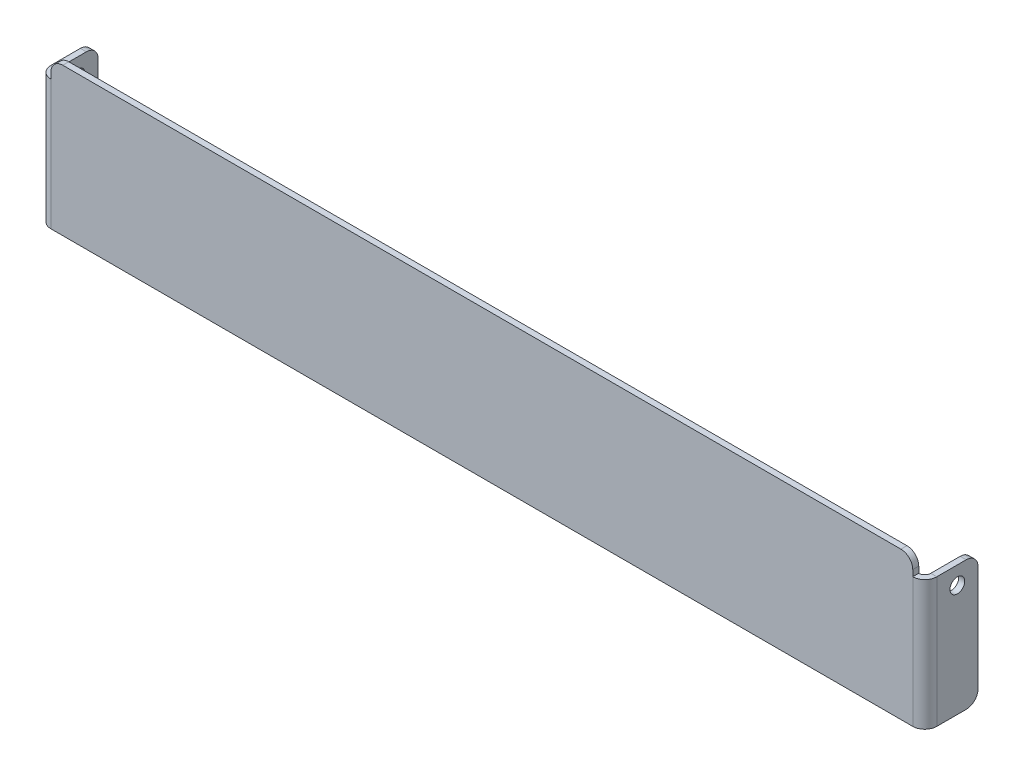
SolidWorks part; units mm, degrees
note: The reader was unsure of these and kept them because the rebuilt part matched: flange length of "Edge-Flange1".
ref_plane "Front Plane" through (0, 0, 0) normal (0, 0, 1) x (1, 0, 0)
ref_plane "Top Plane" through (0, 0, 0) normal (0, 1, 0) x (1, 0, 0)
ref_plane "Right Plane" through (0, 0, 0) normal (1, 0, 0) x (0, 0, -1)
sketch "Sketch2" plane through (0, 0, 0) normal (0, 0, 1) x (1, 0, 0)
  line L0 (75, -24.996) -> (-75, -24.996) construction
  line L1 (-72.968, -24.996) -> (0, -24.996)
  line L2 (-72.968, -24.996) -> (-72.968, 0)
  line L3 (-72.968, 0) -> (0, 0)
  line L4 (0, -24.996) -> (0, 0)
  dimension "D1" = 72.968
base flange "Base-Flange1" sketch "Sketch2" thickness 1.016 reverse thickness direction no parameters "D1"=1.016
edge flange "Edge-Flange1" sketch "Sketch27" flange angle 90 flange length 8 flange position bend outside bend radius 1.016 thickness 1.016 relief rectangular parameters "D6"=10, "D8"=1
bend "EdgeBend3" bend radius 1.016 bend angle 90 parameters "D5"=1
sketch "Sketch27" plane through (-72.968, 0, -1.016) normal (-1, 0, 0) x (0, 1, 0)
  line L2 (-3.048, 0) -> (-3.048, 8)
  line L3 (-3.048, 8) -> (-24.996, 8)
  line L4 (-24.996, 8) -> (-24.996, 0)
  line L5 (0, 0) -> (-24.996, 0) construction
  line L6 (-3.048, 0) -> (-24.996, 0)
  line L7 (0, 0) -> (0, -1.016) construction
  point P7 (0, -0.508)
  dimension "D1" = 3.048
fillet "Fillet1" radius 2 3 edges at (-74.492, -24.996, -9.016) (-74.492, -3.048, -9.016) (-72.968, 0, -0.508)
sketch "Sketch15" plane through (-75, 0, 0) normal (1, 0, 0) x (0, 0, -1)
  line L0 (9.016, -6.048) -> (5.524, -6.048) construction
  line L2 (5.524, -6.048) -> (2.032, -6.048) construction
  line L7 (2.032, -3.048) -> (7.016, -3.048) construction
  dimension "D1" = 3
hole_wizard "Tap Drill for M3x0.5 Tap1" positions "Sketch31" profile "Sketch32" hole size "M3x0.5" standard "ANSI Metric" end condition through all
sketch "Sketch31" plane through (-75, 0, 0) normal (-1, 0, 0) x (0, 0, 1)
  point P0 (-5.524, -6.048)
sketch "Sketch32" plane through (-75, -6.048, -5.524) normal (0, 1, 0) x (0, 0, 1)
  line L0 (0, 0) -> (0, 75)
  line L1 (0, 75) -> (1.25, 75)
  line L2 (1.25, 75) -> (1.25, 0)
  line L5 (1.25, 0) -> (0, 0)
  line L11 (0, -6.35) -> (0, 107.95) construction
  dimension "Thru Hole Dia." = 2.5
  dimension "Thru Hole Depth" = 75
mirror "Mirror1" about plane through (0, -24.996, -1.016) normal (1, 0, 0) of bodies 105
bend "MirrorBend1" bend radius 1.016 bend angle 90 parameters "D5"=2
sketch "Bend-Lines1" [suppressed] plane through (0, 0, 0) normal (0, 1, 0) x (1, 0, 0)
sketch "Bounding-Box1" [suppressed] plane through (0, 0, 0) normal (0, 1, 0) x (1, 0, 0)
sheet metal parameters "Sheet-Metal1" thickness 1.016 parameters "D1"=1.016
flat pattern "Flat-Pattern1" [suppressed]
sketch "Bend-Lines2" plane through (0, 0, 0) normal (0, 1, 0) x (1, 0, 0)
sketch3d "Bounding-Box2" [suppressed]
  line L0 (-75, -15.996, 0) -> (0, -15.996, 0) construction
  line L1 (-75, 0, 0) -> (0, 0, 0) construction
  line L2 (-75, -15.996, 0) -> (-75, 0, 0) construction
  line L3 (0, -15.996, 0) -> (0, 0, 0) construction
sheet metal parameters "Sheet-Metal2" thickness 1.016 parameters "D1"=1.016
flat pattern "Flat-Pattern1"
sketch "Bend-Lines2" plane through (0, 0, 0) normal (0, 0, 1) x (1, 0, 0)
  line L1 (-76.1969, -3.048) -> (-76.1969, -15.996) construction
  line L3 (-76.1969, -3.048) -> (-76.1969, -15.996) construction
sketch3d "Bounding-Box2" [suppressed]
  line L0 (-84.3779, 0, 0) -> (0, 0, 0) construction
  line L1 (-84.3779, -15.996, 0) -> (0, -15.996, 0) construction
  line L2 (-84.3779, 0, 0) -> (-84.3779, -15.996, 0) construction
  line L3 (0, 0, 0) -> (0, -15.996, 0) construction
bend of the flat pattern "Flatten-<EdgeBend3>1"
sheet metal parameters "Sheet-Metal5" thickness 1.016 parameters "D1"=1.016
flat pattern "Flat-Pattern1" [suppressed]
sketch "Bend-Lines2" plane through (0, 0, 0) normal (0, 0, 1) x (1, 0, 0)
  line L1 (-74.1649, -3.048) -> (-74.1649, -15.996) construction
  line L3 (-74.1649, -3.048) -> (-74.1649, -15.996) construction
sketch3d "Bounding-Box2" [suppressed]
  line L0 (-82.3459, 0, 0) -> (0, 0, 0) construction
  line L1 (-82.3459, -15.996, 0) -> (0, -15.996, 0) construction
  line L2 (-82.3459, 0, 0) -> (-82.3459, -15.996, 0) construction
  line L3 (0, 0, 0) -> (0, -15.996, 0) construction
bend of the flat pattern "Flatten-<EdgeBend3>1"
sketch "Sketch15-1" [suppressed] plane through (-73.3299, 0, 0) normal (0, 0, -1) x (-1, 0, 0)
  line L0 (9.016, -9.522) -> (5.524, -9.522) construction
  line L2 (5.524, -9.522) -> (2.032, -9.522) construction
sheet metal parameters "Sheet-Metal6" thickness 1.016 parameters "D1"=1.016
flat pattern "Flat-Pattern6" [suppressed]
sketch "Bend-Lines3" plane through (0, 0, 0) normal (0, 0, 1) x (1, 0, 0)
  line L0 (74.1649, -24.996) -> (74.1649, -3.048) construction
  line L1 (-74.1649, -3.048) -> (-74.1649, -24.996) construction
  line L2 (74.1649, -24.996) -> (74.1649, -3.048) construction
  line L3 (-74.1649, -3.048) -> (-74.1649, -24.996) construction
sketch3d "Bounding-Box3" [suppressed]
  line L0 (-82.3459, 0.0001, 0) -> (82.3459, 0, 0) construction
  line L1 (-82.3459, -24.9959, 0) -> (82.3459, -24.996, 0) construction
  line L2 (-82.3459, 0.0001, 0) -> (-82.3459, -24.9959, 0) construction
  line L3 (82.3459, 0, 0) -> (82.3459, -24.996, 0) construction
bend of the flat pattern "Flatten-<EdgeBend3>2"
bend of the flat pattern "Flatten-<MirrorBend1>1"
sketch "Sketch15-2" plane through (-73.3299, 0, 0) normal (0, 0, -1) x (-1, 0, 0)
  line L0 (9.016, -6.048) -> (5.524, -6.048) construction
  line L2 (5.524, -6.048) -> (2.032, -6.048) construction
  line L7 (-0.3619, -3.048) -> (7.016, -3.048) construction
  dimension "D1" = 3
equation "\"D1@Sketch27\"=\"Thickness\"*3"
equation "\"D1@Sketch2\"=75mm-2*\"Thickness\""
